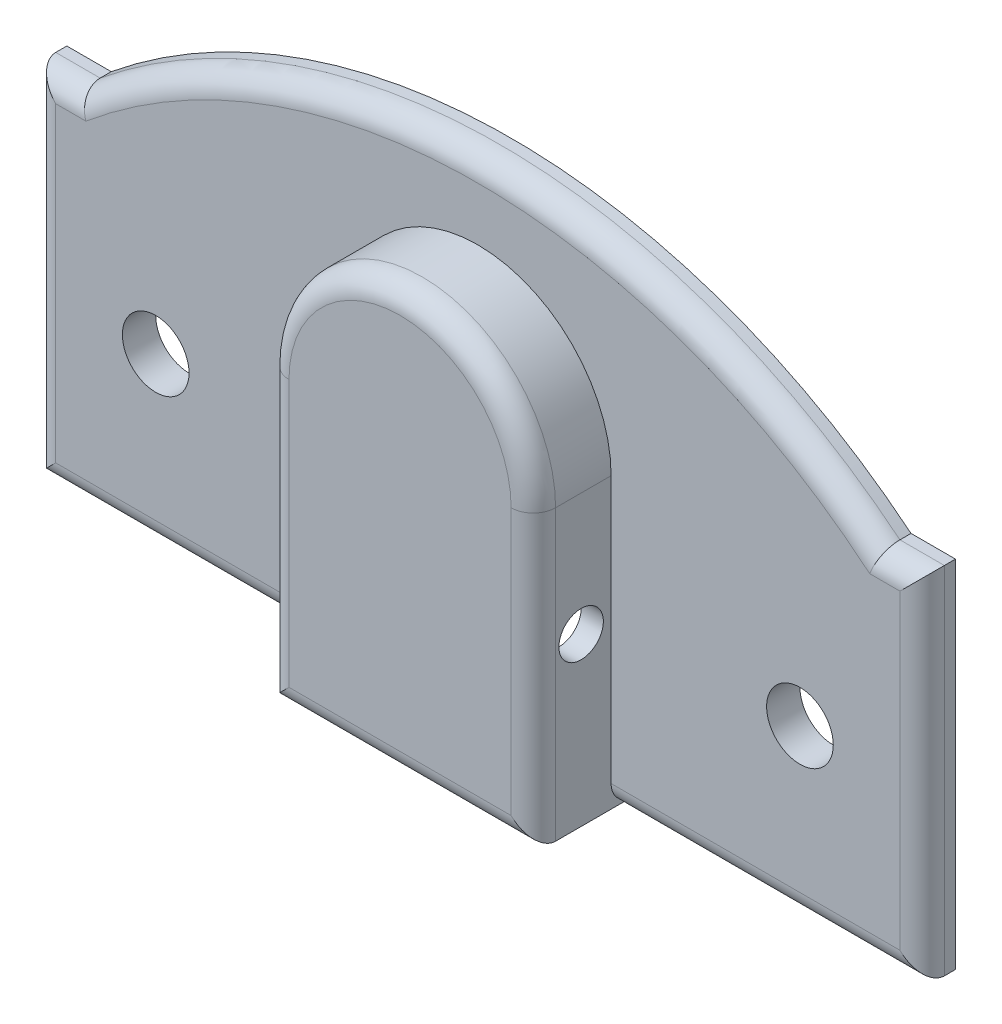
SolidWorks part; units mm, degrees
material "1060 Alloy"
ref_plane "Front" through (0, 0, 0) normal (0, 0, 1) x (1, 0, 0)
ref_plane "Top" through (0, 0, 0) normal (0, 1, 0) x (1, 0, 0)
ref_plane "Right" through (0, 0, 0) normal (1, 0, 0) x (0, 0, -1)
sketch "Sketch1" plane through (0, 0, 0) normal (0, 0, 1) x (1, 0, 0)
  line L0 (0, 0) -> (20, 0)
  line L1 (55, 0) -> (-55, 0) construction
  line L2 (20, 0) -> (20, 16)
  line L4 (-20, 16) -> (-20, 0)
  line L5 (-20, 0) -> (0, 0)
  line L6 (-20, 16) -> (-18, 16)
  line L7 (20, 16) -> (18, 16)
  arc A0 (-18, 16) -> (18, 16) centre (0, -6.0731) cw
  dimension "D3" = 2
  dimension "D5" = 16
  dimension "D7" = 28.4819
  dimension "D1" = 20
  dimension "D2" = 20
  dimension "D4" = 2
  dimension "D6" = 16
extrude "Boss-Extrude1" add sketch "Sketch1" along normal blind 1.5
sketch "Sketch2" plane through (0, 0, 1.5) normal (0, 0, 1) x (1, 0, 0)
  line L1 (0.825, 0) -> (-0.825, 0) construction
  line L2 (6, 0) -> (6, 13)
  line L4 (-6, 0) -> (-6, 13)
  line L5 (-6, 0) -> (6, 0)
  arc A1 (-6, 13) -> (6, 13) centre (0, 13) cw
  dimension "D1" = 6
  dimension "D3" = 13
  dimension "D4" = 13
  dimension "D2" = 6
extrude "Boss-Extrude2" add sketch "Sketch2" along normal blind 3.5 contours A1 L2 L5 L4
sketch "Sketch3" plane through (0, 0, 0) normal (0, 0, -1) x (-1, 0, 0)
  line L0 (0, 0) -> (5, 0)
  line L1 (0.825, 0) -> (-0.825, 0) construction
  line L2 (5, 0) -> (5, 12)
  line L3 (0, 0) -> (-5, 0)
  line L4 (-5, 0) -> (-5, 12)
  arc A0 (-5, 12) -> (5, 12) centre (0, 12) cw
  dimension "D1" = 5
  dimension "D2" = 5
  dimension "D3" = 12
  dimension "D4" = 12
extrude "Cut-Extrude1" cut sketch "Sketch3" against normal blind 4 contours A0 L2 L0 L3 L4
sketch "Sketch4" plane through (-6, 0, 0) normal (-1, 0, 0) x (0, 0, 1)
  line L6 (2.75, 0) -> (-2.75, 0) construction
  circle A0 centre (2.85, 7.5) radius 1
  dimension "D1" = 7.5
  dimension "D2" = 2
  dimension "D3" = 2.15
fillet "Fillet1" radius 1 4 edges at (0, 19, 5) (6, 6.5, 5) (0, 0, 5) (-6, 6.5, 5)
fillet "Fillet4" radius 1 7 edges at (13, 0, 1.5) (20, 8, 1.5) (19, 16, 1.5) (-13, 0, 1.5) (0, 22.4089, 1.5) (-19, 16, 1.5) (-20, 8, 1.5)
sketch "Sketch5" plane through (0, 0, 1.5) normal (0, 0, 1) x (1, 0, 0)
  line L0 (-19, 1) -> (-6, 1) construction
  line L1 (0, -2.75) -> (0, 2.75) construction
  circle A0 centre (-14.4996, 7.5) radius 1.5
  circle A1 centre (14.4996, 7.5) radius 1.5
  dimension "D1" = 3
  dimension "D2" = 6.5
  dimension "D3" = 4.5004
extrude "Cut-Extrude3" cut sketch "Sketch5" against normal blind 12 contours A1 | A0 region at (14.4996, 7.5, 1.5)
extrude "Cut-Extrude5" cut sketch "Sketch4" against normal blind 20 contours A0
